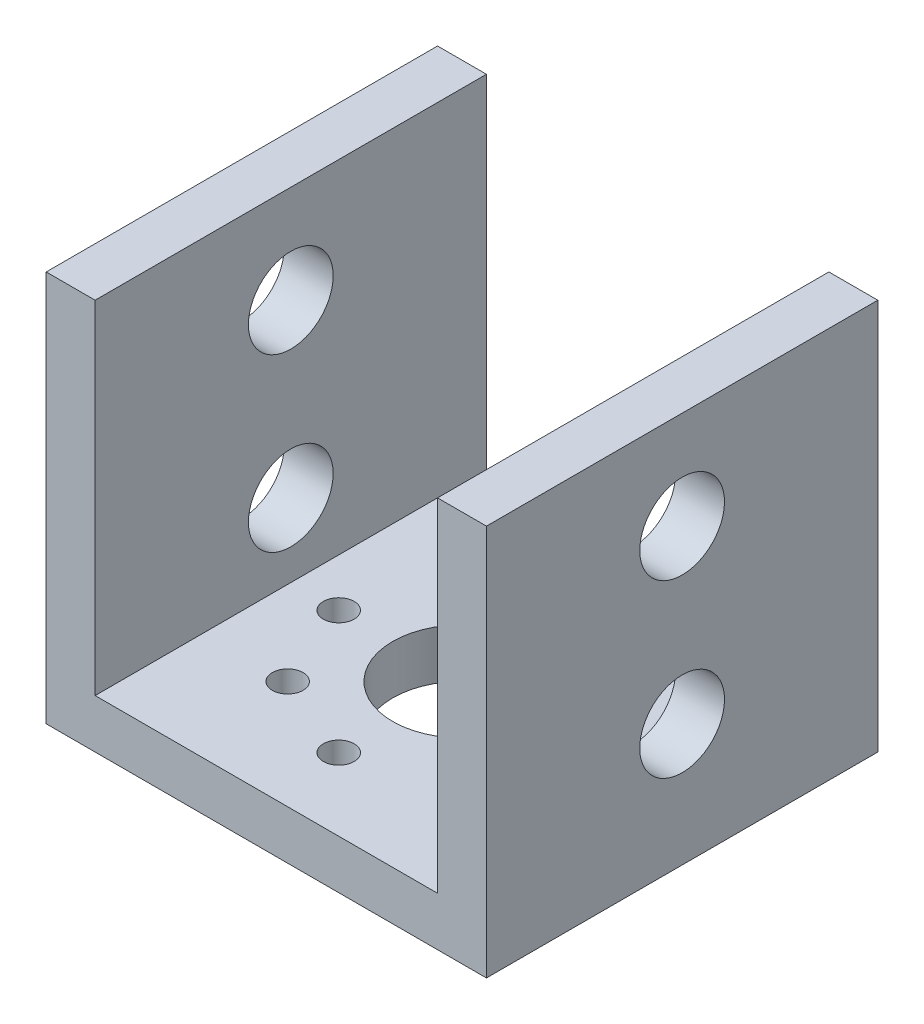
SolidWorks part; units mm, degrees
material "6063-T5"
ref_plane "Front Plane" through (0, 0, 0) normal (0, 0, 1) x (1, 0, 0)
ref_plane "Top Plane" through (0, 0, 0) normal (0, 1, 0) x (1, 0, 0)
ref_plane "Right Plane" through (0, 0, 0) normal (1, 0, 0) x (0, 0, -1)
sketch "Sketch1" plane through (0, 0, 0) normal (0, 0, 1) x (1, 0, 0)
  line L0 (-11.1125, 0) -> (11.1125, 0)
  line L1 (0, 0) -> (0, -3.175) construction
  line L2 (-14.2875, -3.175) -> (14.2875, -3.175)
  line L3 (14.2875, -3.175) -> (14.2875, 22.225)
  line L4 (-14.2875, -3.175) -> (-14.2875, 22.225)
  line L5 (-11.1125, 0) -> (-11.1125, 22.225)
  line L6 (-11.1125, 22.225) -> (-14.2875, 22.225)
  line L7 (11.1125, 0) -> (11.1125, 22.225)
  line L8 (11.1125, 22.225) -> (14.2875, 22.225)
  point P3 (0, 0)
  point P9 (0, -3.175)
  dimension "D1" = 22.225
  dimension "D2" = 3.175
  dimension "D3" = 28.575
  dimension "D4" = 25.4
extrude "Boss-Extrude1" add sketch "Sketch1" along normal blind 25.4
sketch "Sketch2" plane through (14.2875, 0, 0) normal (1, 0, 0) x (0, 0, -1)
  line L0 (-25.4, 22.225) -> (0, 22.225) construction
  line L1 (-25.4, -3.175) -> (-25.4, 22.225) construction
  line L3 (-25.4, -3.175) -> (0, -3.175) construction
  circle A0 centre (-12.7, 15.875) radius 2.75
  circle A1 centre (-12.7, 4.7625) radius 2.75
  point P6 (-12.7, 22.225)
  dimension "D1" = 5.5
  dimension "D4" = 7.9375
  dimension "D2" = 6.35
  dimension "D3" = 12.7
extrude "Cut-Extrude1" cut sketch "Sketch2" against normal through all
sketch "Sketch3" plane through (0, 0, 0) normal (0, 1, 0) x (1, 0, 0)
  line L0 (-11.1125, 0) -> (11.1125, -25.4) construction
  circle A0 centre (0, -12.7) radius 4.5
  point P6 (0, -4.7)
  point P10 (5.6569, -7.0431)
  point P11 (8, -12.7)
  point P12 (5.6569, -18.3569)
  point P13 (0, -20.7)
  point P14 (-5.6569, -18.3569)
  point P15 (-8, -12.7)
  point P16 (-5.6569, -7.0431)
  point P17 (0, -12.7)
  dimension "D1" = 9
  dimension "D2" = 8
  dimension "D3" = 8
extrude "Cut-Extrude2" cut sketch "Sketch3" against normal through all
hole_wizard "Ø2.0mm Dowel Hole1" positions "Sketch4" profile "Sketch5" hole size "Ø2.0" standard "ISO" end condition through all
sketch "Sketch4" plane through (0, 0, 0) normal (0, 1, 0) x (1, 0, 0)
  point P0 (0, -4.7)
  point P3 (5.6569, -7.0431)
  point P6 (8, -12.7)
  point P9 (5.6569, -18.3569)
  point P12 (0, -20.7)
  point P15 (-5.6569, -18.3569)
  point P18 (-8, -12.7)
  point P21 (-5.6569, -7.0431)
sketch "Sketch5" plane through (0, 0, 4.7) normal (1, 0, 0) x (0, 0, 1)
  line L0 (0, 0) -> (0, 3.175)
  line L1 (0, 3.175) -> (1, 3.175)
  line L2 (1, 3.175) -> (1, 0)
  line L5 (1, 0) -> (0, 0)
  line L11 (0, -6.35) -> (0, 107.95) construction
  dimension "Thru Hole Dia." = 2
  dimension "Thru Hole Depth" = 3.175
